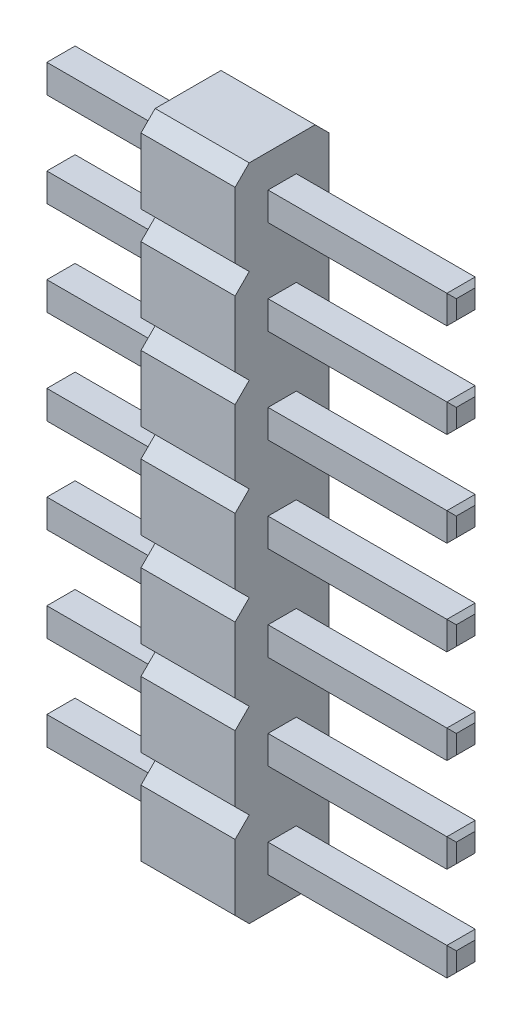
SolidWorks part; units mm, degrees
ref_plane "Front Plane" through (0, 0, 0) normal (0, 0, 1) x (1, 0, 0)
ref_plane "Top Plane" through (0, 0, 0) normal (0, 1, 0) x (1, 0, 0)
ref_plane "Right Plane" through (0, 0, 0) normal (1, 0, 0) x (0, 0, -1)
sketch "Sketch1" plane through (0, 0, 0) normal (1, 0, 0) x (0, 0, -1)
  line L0 (0, 0) -> (-1, 0) construction
  line L5 (-1, 0) -> (-1, 1) construction
  line L6 (-1.7, 1) -> (-0.3, 1)
  line L7 (-0.3, 1) -> (0, 0.7)
  line L8 (0, 0.7) -> (0, -0.7)
  line L9 (-2, 0.7) -> (-2, -0.7)
  line L10 (-1.7, 1) -> (-2, 0.7)
  line L11 (-0.3, -1) -> (0, -0.7)
  line L12 (-1.7, -1) -> (-0.3, -1)
  line L13 (-1.7, -1) -> (-2, -0.7)
  point P13 (-2, 0)
  dimension "D1" = 1
  dimension "D2" = 45
  dimension "D3" = 0.3
extrude "Plastic" add sketch "Sketch1" along normal blind 2
sketch "Sketch2" plane through (0, 0, 0) normal (0, 1, 0) x (1, 0, 0)
  line L0 (-2.8, -0.7) -> (-2.8, -1.3)
  line L1 (-2.8, -1) -> (5.9, -1) construction
  line L2 (0, -1.7) -> (0, -0.3) construction
  line L4 (-2.8, -1.3) -> (5.9, -1.3)
  line L6 (-2.8, -0.7) -> (5.9, -0.7)
  line L8 (5.9, -1.3) -> (5.9, -0.7)
  line L9 (2, -0.3) -> (2, -1.7) construction
  line L10 (0, -0.3) -> (0, -1.7) construction
  line L11 (-3.4, 3.63) -> (-3.4, -0.4) construction
  line L12 (-3.7, 3.63) -> (-3.7, -0.4) construction
  line L13 (-3.1, 3.63) -> (-3.1, -0.4) construction
  arc A3 (-3.7, -0.4) -> (-2.8, -1.3) centre (-2.8, -0.4) ccw construction
  arc A4 (-3.4, -0.4) -> (-2.8, -1) centre (-2.8, -0.4) ccw construction
  arc A5 (-3.1, -0.4) -> (-2.8, -0.7) centre (-2.8, -0.4) ccw construction
  point P5 (0, -1)
  dimension "D1" = 3.9
  dimension "D4" = 8.7
  dimension "D5" = 2.8
  dimension "D2" = 0.3
  dimension "D3" = 0.3
extrude "Contact" add sketch "Sketch2" along normal mid plane 0.6
chamfer "Chamfer1" distance 0.1 angle 45 8 edges at (5.9, 0.3, 1) (5.9, 0, 1.3) (5.9, -0.3, 1) (5.9, 0, 0.7) (-2.8, -0.3, 1) (-2.8, 0, 0.7) (-2.8, 0.3, 1) (-2.8, 0, 1.3)
pattern_linear "LPattern1" count 7 spacing 2 along (0, 1, 0) of "Plastic", "Contact", "Chamfer1"
sketch "Sketch3" plane through (5.9, 0, 0) normal (1, 0, 0) x (0, 0, -1)
  line L0 (-1.2, 10) -> (-1, 10) construction
  line L1 (-1.2, 10.2) -> (-1.2, 9.8) construction
  line L2 (-1, 10) -> (-1, 10.2) construction
  line L3 (-0.8, 10.2) -> (-1.2, 10.2) construction
ref_axis "Axis1" through (5.9, 10, 1) along (-1, 0, 0)
ref_plane "Plane1" through (0, 6, 0) normal (0, 1, 0) x (1, 0, 0)
ref_plane "Plane2" through (0, 0, 1) normal (0, 0, 1) x (1, 0, 0)
